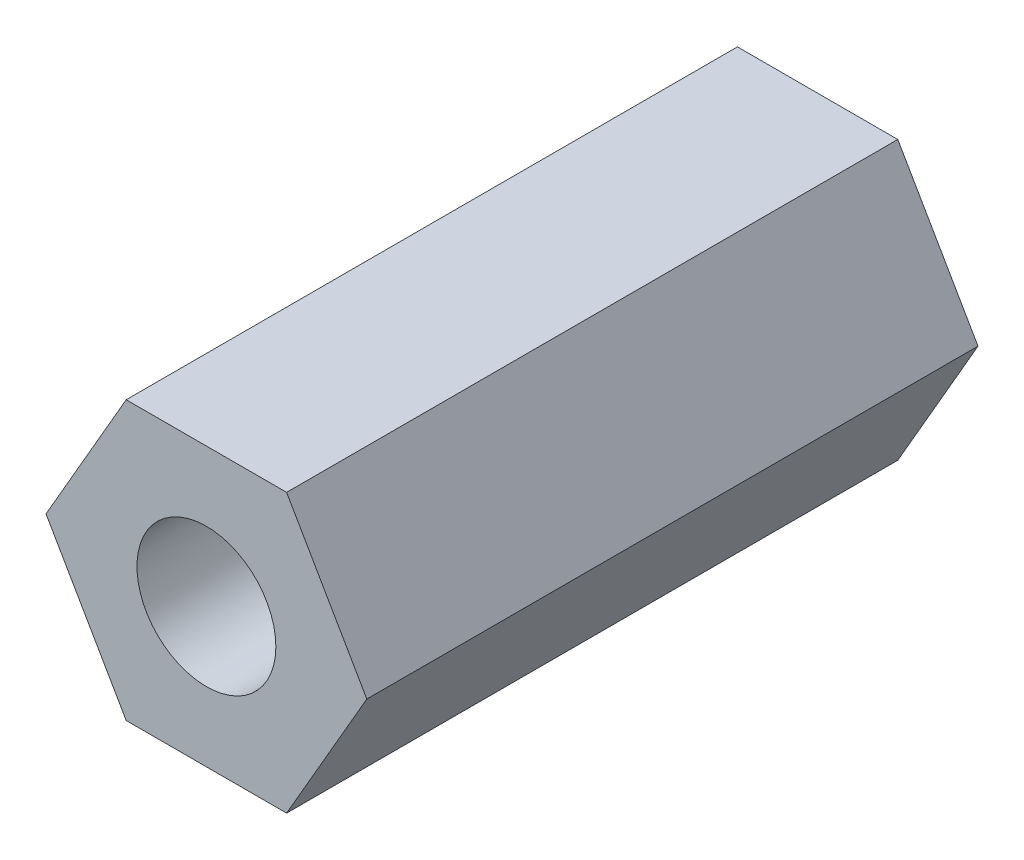
SolidWorks part; units mm, degrees
ref_plane "Front Plane" through (0, 0, 0) normal (0, 0, 1) x (1, 0, 0)
ref_plane "Top Plane" through (0, 0, 0) normal (0, 1, 0) x (1, 0, 0)
ref_plane "Right Plane" through (0, 0, 0) normal (1, 0, 0) x (0, 0, -1)
sketch "Sketch1" plane through (0, 0, 0) normal (0, 0, 1) x (1, 0, 0)
  line L0 (2.8868, 0) -> (1.4434, 2.5)
  line L1 (1.4434, 2.5) -> (-1.4434, 2.5)
  line L2 (-1.4434, 2.5) -> (-2.8868, 0)
  line L3 (-2.8868, 0) -> (-1.4434, -2.5)
  line L4 (-1.4434, -2.5) -> (1.4434, -2.5)
  line L5 (1.4434, -2.5) -> (2.8868, 0)
  circle A0 centre (0, 0) radius 1.25
extrude "Hex" add sketch "Sketch1" along normal blind 11
equation "\"af\" = 5mm"
equation "\"bore_d\" = 2.5mm"
equation "\"length\" = 11mm"
equation "\"D1@Hex\" = \"length\""
